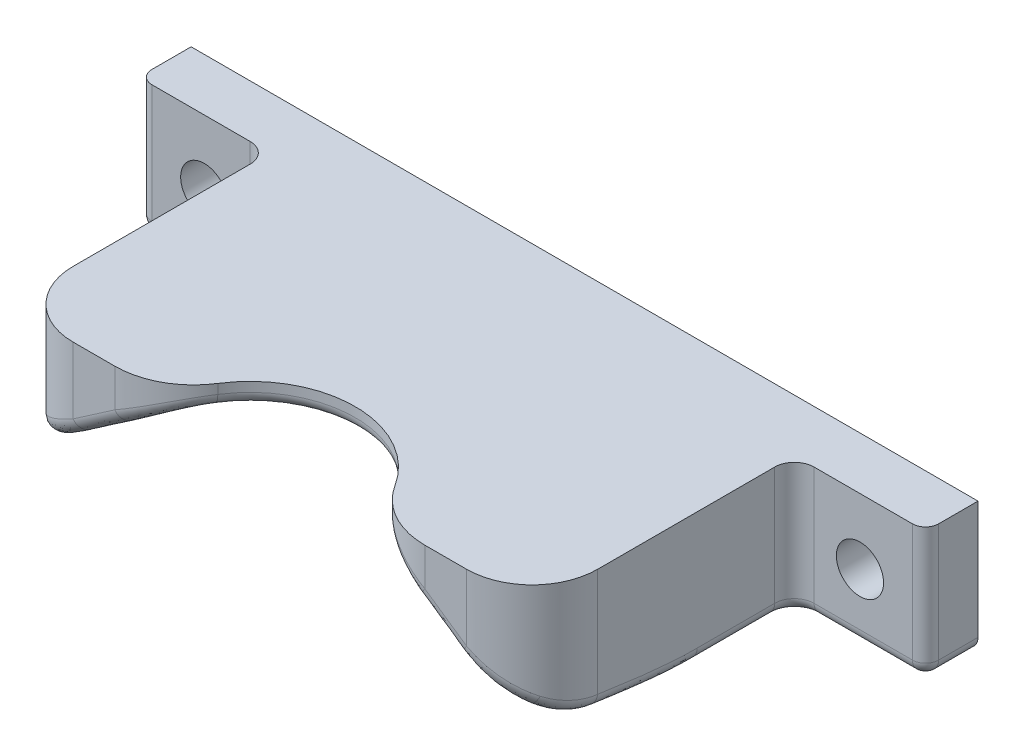
SolidWorks part; units mm, degrees
ref_plane "正面" through (0, 0, 0) normal (0, 0, 1) x (1, 0, 0)
ref_plane "平面" through (0, 0, 0) normal (0, 1, 0) x (1, 0, 0)
ref_plane "右側面" through (0, 0, 0) normal (1, 0, 0) x (0, 0, -1)
sketch "ｽｹｯﾁ1" plane through (0, 0, 0) normal (0, 0, 1) x (1, 0, 0)
  line L1 (-30, 115) -> (30, 115)
  line L2 (-30, 115) -> (-30, 105)
  line L3 (-30, 105) -> (30, 105)
  line L4 (30, 115) -> (30, 105)
extrude "ﾎﾞｽ - 押し出し1" add sketch "ｽｹｯﾁ1" along normal blind 4
sketch "ｽｹｯﾁ2" plane through (0, 0, 4) normal (0, 0, 1) x (1, 0, 0)
  line L0 (30, 115) -> (-30, 115) construction
  line L1 (-20, 115) -> (20, 115)
  line L2 (-20, 115) -> (-20, 105)
  line L3 (-20, 105) -> (20, 105)
  line L4 (20, 115) -> (20, 105)
  line L5 (-30, 105) -> (30, 105) construction
  line L6 (-30, 115) -> (-30, 105) construction
  line L7 (30, 105) -> (30, 115) construction
  dimension "D1" = 10
  dimension "D2" = 10
extrude "ﾎﾞｽ - 押し出し2" add sketch "ｽｹｯﾁ2" along normal blind 20
sketch "ｽｹｯﾁ3" plane through (0, 105, 0) normal (0, -1, 0) x (-1, 0, 0)
  line L0 (20, -24) -> (-20, -24) construction
  circle A0 centre (0, -25.5) radius 8
  point P4 (0, -24)
  dimension "D2" = 16
  dimension "D1" = 0
  dimension "D3" = 1.5
extrude "ｶｯﾄ - 押し出し1" cut sketch "ｽｹｯﾁ3" against normal blind 20
chamfer "面取り1" distance 12.5 angle 35 1 edges at (0, 105, 17.5) first distance on face at (0, 105, 10.55)
fillet "ﾌｨﾚｯﾄ1" radius 5 2 edges at (20, 110.1554, 24) (-20, 110.1554, 24)
fillet "ﾌｨﾚｯﾄ2" radius 6 2 edges at (7.8581, 114.3763, 24) (-7.8581, 114.3763, 24)
fillet "ﾌｨﾚｯﾄ3" radius 1 2 edges at (30, 110, 4) (-30, 110, 4)
fillet "ﾌｨﾚｯﾄ4" radius 10 1 edges at (0, 105, 5)
sketch "ｽｹｯﾁ4" plane through (0, 0, 0) normal (0, 0, -1) x (-1, 0, 0)
  circle A0 centre (25, 110) radius 1.8
  circle A1 centre (-25, 110) radius 1.8
  dimension "D1" = 3.6
  dimension "D2" = 3.6
extrude "ｶｯﾄ - 押し出し2" cut sketch "ｽｹｯﾁ4" against normal blind 20
fillet "ﾌｨﾚｯﾄ5" radius 1.5 2 edges at (20, 110, 4) (-20, 110, 4)
fillet "ﾌｨﾚｯﾄ6" radius 1 21 edges at (-30, 105, 1.5) (-29.7071, 105, 3.7071) (-25.25, 105, 4) (-20.4393, 105, 4.4393) (-20, 105, 9.1861) (30, 105, 1.5) (29.7071, 105, 3.7071) (25.25, 105, 4) (20.4393, 105, 4.4393) (20, 105, 9.1861) (19.6757, 105.6019, 20.7714) (16.3709, 107.8302, 23.8084) (7.9598, 113.4205, 22.592) (0, 113.7526, 17.5) (-8.9855, 112.8746, 23.2874) (-19.0125, 105.9803, 21.9832)
